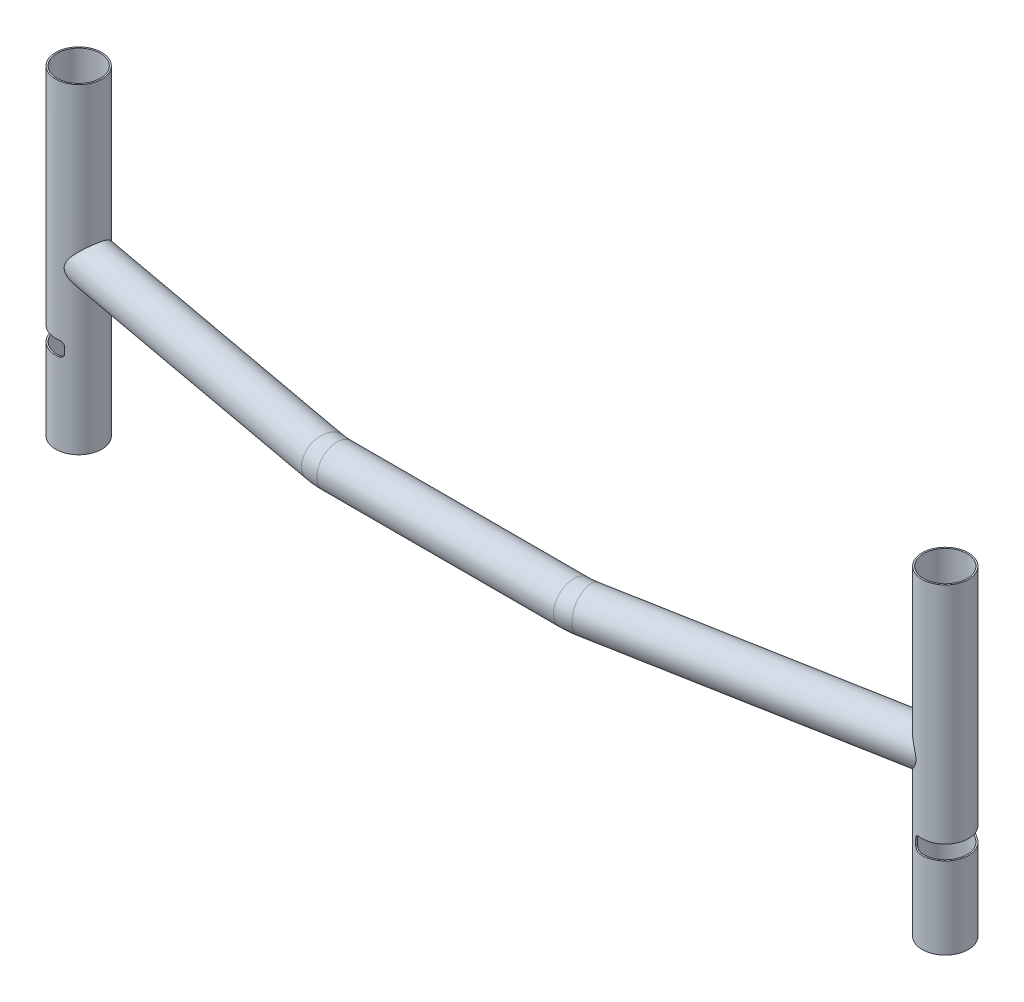
SolidWorks part; units mm, degrees
ref_plane "Front Plane" through (0, 0, 0) normal (0, 0, 1) x (1, 0, 0)
ref_plane "Top Plane" through (0, 0, 0) normal (0, 1, 0) x (1, 0, 0)
ref_plane "Right Plane" through (0, 0, 0) normal (1, 0, 0) x (0, 0, -1)
sketch "Sketch1" plane through (0, 0, 0) normal (0, 1, 0) x (1, 0, 0)
  line L0 (0, 0) -> (0, 107.988) construction
  line L1 (-65, 0) -> (65, 0)
  line L2 (72.225, 0.6579) -> (232, 30)
  line L3 (-72.225, 0.6579) -> (-232, 30)
  arc A0 (72.225, 0.6579) -> (65, 0) centre (65, 40) cw
  arc A1 (-72.225, 0.6579) -> (-65, 0) centre (-65, 40) ccw
  dimension "D2" = 40
  dimension "D1" = 232
  dimension "D3" = 65
  dimension "D4" = 30
ref_plane "Plane1" through (232, 0, -30) normal (0.9836, 0, -0.1806) x (-0.1806, 0, -0.9836)
sketch "Sketch2" plane through (232, 0, -30) normal (0.9836, 0, -0.1806) x (-0.1806, 0, -0.9836)
  line L0 (0.6579, 0) -> (0, 0) construction
  circle A0 centre (0, 0) radius 11.1
  circle A1 centre (0, 0) radius 10.3
  dimension "D1" = 0.8
sweep "Sweep1" add profiles "Sketch2" path "Sketch1"
sketch "Sketch3" plane through (0, 0, 0) normal (0, 1, 0) x (1, 0, 0)
  line L0 (229.9951, 40.9174) -> (234.0049, 19.0826) construction
  line L1 (229.9951, 40.9174) -> (232, 30) construction
  line L2 (232, 30) -> (237.9013, 31.0838) construction
  circle A0 centre (237.9013, 31.0838) radius 12.7
  circle A1 centre (237.9013, 31.0838) radius 11.9
  dimension "D1" = 0.8
  dimension "D3" = 25.4
  dimension "D4" = 0.8
  dimension "D2" = 6
extrude "Boss-Extrude1" add sketch "Sketch3" along normal blind 88 and the other way blind 88
sketch "Sketch4" plane through (0, -88, 0) normal (0, -1, 0) x (1, 0, 0)
  circle A0 centre (237.9013, -31.0838) radius 11.9
extrude "Cut-Extrude1" cut sketch "Sketch4" against normal through all
sketch "Sketch5" plane through (232, 0, -30) normal (0.9836, 0, -0.1806) x (-0.1806, 0, -0.9836)
  circle A0 centre (-0.0149, 0) radius 10.7
  dimension "D1" = 21.4
extrude "Cut-Extrude2" cut sketch "Sketch5" against normal blind 88
sketch "Sketch6" plane through (0, 88, 0) normal (0, 1, 0) x (1, 0, 0)
  line L0 (237.9013, 31.0838) -> (72.225, 0.6579)
  line L1 (70.2201, 11.5753) -> (74.23, -10.2595) construction
  line L2 (237.9013, 31.0838) -> (241.892, 42.2947)
  circle A0 centre (237.9013, 31.0838) radius 11.9 construction
  dimension "D1" = 60
ref_plane "Plane2" through (237.9013, 88, -31.0838) normal (0.3353, 0, -0.9421) x (-0.9421, 0, -0.3353)
sketch "Sketch7" plane through (237.9013, 88, -31.0838) normal (0.3353, 0, -0.9421) x (-0.9421, 0, -0.3353)
  line L0 (0, -176) -> (0, -127.2306) construction
  line L1 (-12.7, -176) -> (12.7, -176) construction
  line L4 (-2.5, -123.2306) -> (-12.7, -123.2306)
  line L5 (-2.5, -131.2306) -> (-12.7, -131.2306)
  line L6 (-12.7, -123.2306) -> (-12.7, -131.2306)
  line L7 (0, -125.7306) -> (0, -128.7306)
  arc A0 (0, -125.7306) -> (-2.5, -123.2306) centre (-2.5, -125.7306) ccw
  arc A1 (0, -128.7306) -> (-2.5, -131.2306) centre (-2.5, -128.7306) cw
  dimension "D1" = 2.5
extrude "Cut-Extrude3" cut sketch "Sketch7" against normal blind 20 and the other way blind 20
mirror "Mirror1" about plane through (0, 0, 0) normal (1, 0, 0) of "Cut-Extrude1", "Boss-Extrude1", "Cut-Extrude3", "Cut-Extrude2"
sketch "Sketch8" plane through (0, 0, 0) normal (0, 1, 0) x (1, 0, 0)
  line L0 (72.225, 0.6579) -> (216.9875, 26.5937) construction
  line L1 (70.2201, 11.5753) -> (74.23, -10.2595) construction
  circle A0 centre (216.9875, 26.5937) radius 3
extrude "Cut-Extrude4" cut sketch "Sketch8" against normal up to next
